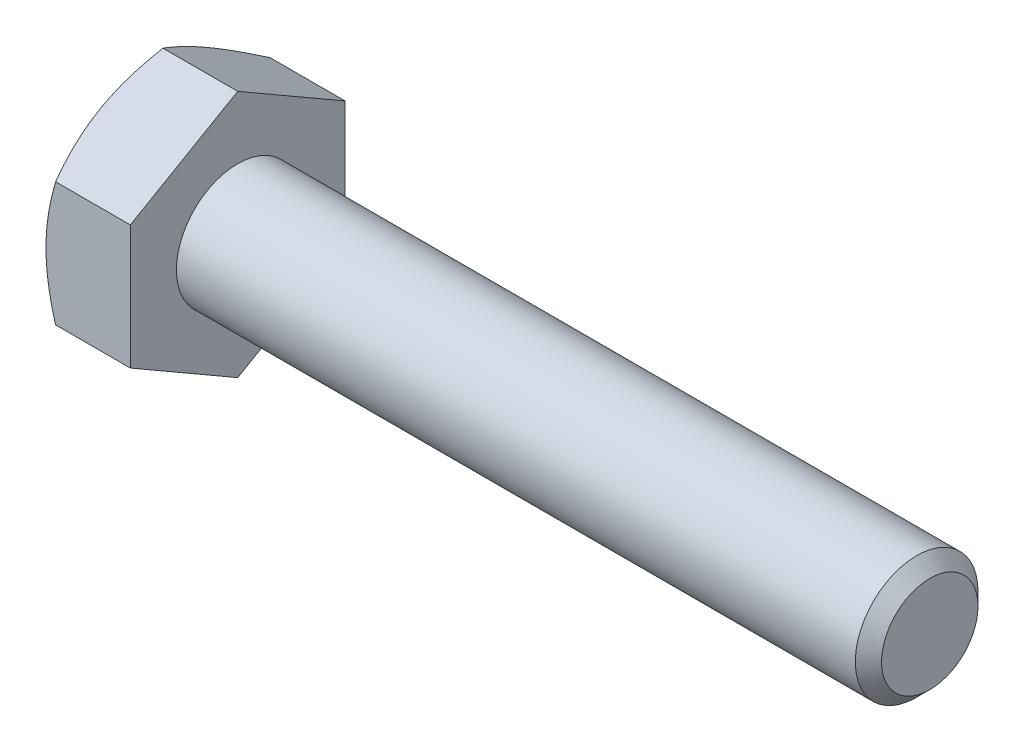
SolidWorks part; units mm, degrees
material "Alloy Steel"
ref_plane "Front Plane" through (0, 0, 0) normal (0, 0, 1) x (1, 0, 0)
ref_plane "Top Plane" through (0, 0, 0) normal (0, 1, 0) x (1, 0, 0)
ref_plane "Right Plane" through (0, 0, 0) normal (1, 0, 0) x (0, 0, -1)
sketch "Sketch1" plane through (0, 0, 0) normal (0, 0, 1) x (1, 0, 0)
  line L0 (-20.0898, 0) -> (20.0898, 0) construction
  line L1 (20.0898, 3.175) -> (20.0898, -3.175) construction
  line L2 (-15.7242, 5.5562) -> (-15.7242, -5.5562) construction
  line L3 (-20.0898, 5.5562) -> (-20.0898, -5.5562) construction
  point P9 (-15.7242, 0)
  point P10 (16.9148, -3.175)
  dimension "Screw Dia" = 6.35
  dimension "Hex" = 11.1125
  dimension "Head Ht" = 4.3656
  dimension "Screw Lenght" = 35.814
  dimension "D1" = 3.175
ref_plane "Plane2" through (20.0898, 0, 0) normal (1, 0, 0) x (0, 0, -1)
sketch "Sketch5" plane through (20.0898, 0, 0) normal (1, 0, 0) x (0, 0, -1)
  circle A0 centre (0, 0) radius 3.175
extrude "Boss-Extrude3" add sketch "Sketch5" against normal up to vertex (35.814 mm away) up to point (-15.7242, 0, 0)
sketch "Sketch9" plane through (20.0898, 0, 0) normal (1, 0, 0) x (0, 0, -1)
  circle A1 centre (0, 0) radius 3.175
  circle A2 centre (0, 0) radius 3.175
  dimension "D1" = 0
curve "Helix/Spiral1" [suppressed] pitch 0.9071 height 19.9571 turns 22 parameters "Pitch"=0.9071
chamfer "Chamfer1" distance 0.6804 angle 45 1 edges at (20.0898, 0, -3.175)
sketch "Sketch10" plane through (0, 0, 0) normal (0, 0, 1) x (1, 0, 0)
  line L0 (20.0898, 3.175) -> (20.43, 2.5858)
  line L1 (20.43, 2.5858) -> (20.5434, 2.5858)
  line L2 (20.5434, 2.5858) -> (20.8836, 3.175)
  line L3 (20.0898, 3.175) -> (20.8836, 3.175)
  line L4 (20.4867, 3.175) -> (20.4867, 2.5858) construction
  line L5 (20.2599, 2.8804) -> (20.7135, 2.8804) construction
  dimension "D1" = 60
  dimension "D2" = 0.1134
  dimension "D3" = 0.4536
sweep "Cut-Sweep1" [suppressed] cut profiles "Sketch10" path "Helix/Spiral1"
sketch "Sketch11" plane through (0, 0, 0) normal (0, 0, 1) x (1, 0, 0)
  line L0 (-15.7242, 3.175) -> (-15.7242, 0)
  line L1 (-15.7242, 0) -> (4.2148, 0)
  line L3 (4.2148, 0) -> (1.0398, 3.175)
  line L4 (-15.7242, 3.175) -> (1.0398, 3.175)
  dimension "D1" = 45
  dimension "MIn Thread" = 19.05
revolve "Revolve1" [suppressed] add sketch "Sketch11" angle 360 about L1
sketch "Sketch6" plane through (-15.7242, 0, 0) normal (-1, 0, 0) x (0, 0, 1)
  line L0 (0, 5.5562) -> (0, -5.5562) construction
  line L1 (5.5563, 3.2079) -> (0, 6.4158)
  line L2 (0, 6.4158) -> (-5.5562, 3.2079)
  line L3 (-5.5562, 3.2079) -> (-5.5562, -3.2079)
  line L4 (-5.5562, -3.2079) -> (0, -6.4158)
  line L5 (0, -6.4158) -> (5.5563, -3.2079)
  line L6 (5.5563, -3.2079) -> (5.5563, 3.2079)
  circle A0 centre (0, 0) radius 5.5562 construction
extrude "Boss-Extrude4" add sketch "Sketch6" along normal up to vertex (4.3656 mm away) up to point (-20.0898, -5.5562, 0)
sketch "Sketch7" plane through (-20.0898, 0, 0) normal (-1, 0, 0) x (0, 0, 1)
  circle A0 centre (0, 0) radius 5.5562 construction
  circle A1 centre (0, 0) radius 5.5562
sketch "Sketch8" plane through (-20.0898, 0, 0) normal (-1, 0, 0) x (0, 0, 1)
  circle A0 centre (0, 0) radius 5.5562 construction
  circle A1 centre (0, 0) radius 5.5562
extrude "Cut-Extrude3" cut sketch "Sketch8" against normal through all draft 60 flip side to cut
sketch "Sketch12" plane through (-20.0898, 0, 0) normal (-1, 0, 0) x (0, 0, 1)
  line L0 (0, 4.2783) -> (0, 2.3892) construction
  line L1 (0.1667, 4.2783) -> (0.1667, 2.3892)
  line L2 (-0.1667, 4.2783) -> (-0.1667, 2.3892)
  line L3 (0, 3.175) -> (0, -3.175) construction
  arc A0 (0.1667, 4.2783) -> (-0.1667, 4.2783) centre (0, 4.2783) ccw
  arc A1 (-0.1667, 2.3892) -> (0.1667, 2.3892) centre (0, 2.3892) ccw
  circle A3 centre (0, 0) radius 2.2225 construction
  circle A4 centre (0, 0) radius 4.445 construction
  point P2 (0, 3.3337)
  dimension "D1" = 4.445
  dimension "D3" = 8.89
  dimension "D2" = 0.3334
extrude "Cut-Extrude4" [suppressed] cut sketch "Sketch12" against normal blind 0.254
pattern_circular "CirPattern1" [suppressed] count 6 over 360 of bodies 116
equation "\"D2@Sketch10\" = \"Pitch@Helix/Spiral1\"*.125"
equation "\"D3@Sketch10\" = \"Pitch@Helix/Spiral1\"*.5"
equation "\"D3@Helix/Spiral1\" = \"MIn Thread@Sketch11\"+\"Pitch@Helix/Spiral1\""
equation "\"D1@Chamfer1\" = \"Pitch@Helix/Spiral1\"*.75"
equation "\"D1@Sketch12\" = \"Hex@Sketch1\"*.4"
equation "\"D3@Sketch12\" = \"Hex@Sketch1\"*.8"
equation "\"D2@Sketch12\" = \"Hex@Sketch1\"*.03"
equation "\"D1@Sketch1\" = \"Pitch@Helix/Spiral1\"*3.5"
